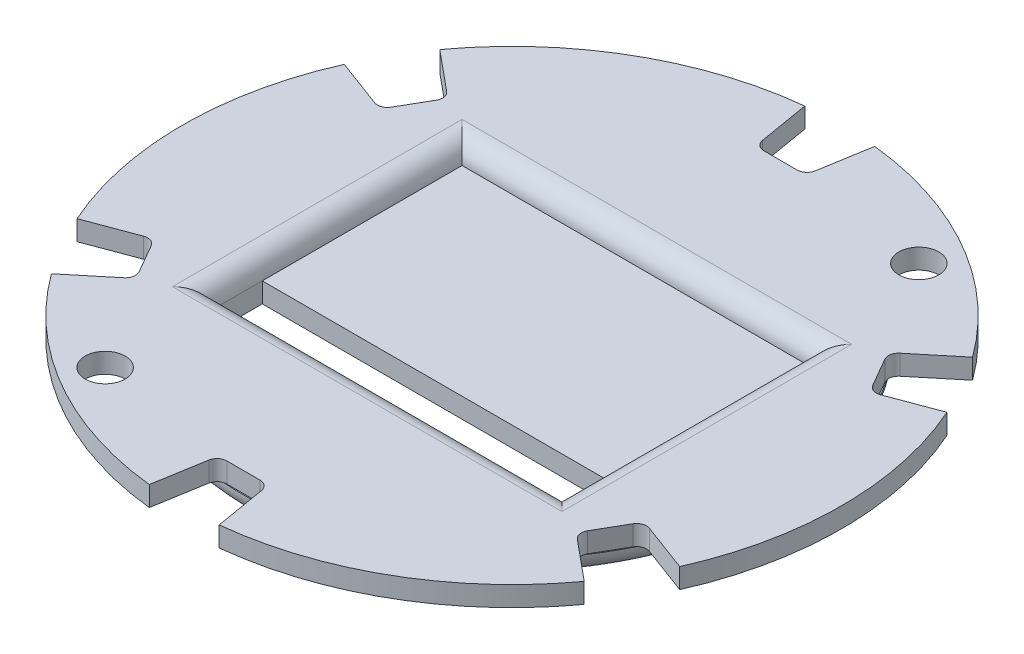
SolidWorks part; units mm, degrees
ref_plane "Front Plane" through (0, 0, 0) normal (0, 0, 1) x (1, 0, 0)
ref_plane "Top Plane" through (0, 0, 0) normal (0, 1, 0) x (1, 0, 0)
ref_plane "Right Plane" through (0, 0, 0) normal (1, 0, 0) x (0, 0, -1)
sketch "Sketch1" plane through (0, 0, 0) normal (0, 1, 0) x (1, 0, 0)
  circle A0 centre (0, 0) radius 33
  dimension "D1" = 66
extrude "Boss-Extrude1" add sketch "Sketch1" along normal blind 2
sketch "Sketch5" plane through (0, 0, 0) normal (0, -1, 0) x (1, 0, 0)
  circle A0 centre (0, 0) radius 27
  circle A2 centre (0, 0) radius 33 construction
  dimension "D1" = 6
extrude "Boss-Extrude2" add sketch "Sketch5" along normal blind 2
sketch "Sketch6" plane through (0, 0, 0) normal (0, -1, 0) x (1, 0, 0)
  line L1 (3.5, 32.8139) -> (2.6406, 27.7177)
  line L7 (-2.6406, 27.7177) -> (-3.5, 32.8139)
  line L9 (0, -33) -> (0, 33) construction
  line L10 (15.8503, -24.88) -> (-15.8503, 24.88) construction
  line L26 (32.8139, -3.5) -> (26.9836, -2.5168) [skipped]
  line L27 (30.1676, 13.3758) -> (25.3245, 11.572)
  line L28 (22.684, 16.1457) -> (26.6676, 19.438)
  line L29 (22.455, 14.8749) -> (24.1095, 12.0092)
  line L30 (26.9836, 2.5168) -> (32.8139, 3.5) [skipped]
  line L31 (-3.5, -32.8139) -> (-2.5168, -26.9836) [skipped]
  line L32 (26.6676, -19.438) -> (22.684, -16.1457)
  line L33 (25.3245, -11.572) -> (30.1676, -13.3758)
  line L34 (24.1095, -12.0092) -> (22.455, -14.8749)
  line L35 (2.5168, -26.9836) -> (3.5, -32.8139) [skipped]
  line L36 (-32.8139, 3.5) -> (-26.9836, 2.5168) [skipped]
  line L37 (-3.5, -32.8139) -> (-2.6406, -27.7177)
  line L38 (2.6406, -27.7177) -> (3.5, -32.8139)
  line L39 (1.6545, -26.884) -> (-1.6545, -26.884)
  line L40 (-26.9836, -2.5168) -> (-32.8139, -3.5) [skipped]
  line L66 (-1.6545, 26.884) -> (1.6545, 26.884)
  line L67 (-30.1676, -13.3758) -> (-25.3245, -11.572)
  line L68 (-22.684, -16.1457) -> (-26.6676, -19.438)
  line L69 (-22.455, -14.8749) -> (-24.1095, -12.0092)
  line L70 (-26.6676, 19.438) -> (-22.684, 16.1457)
  line L71 (-25.3245, 11.572) -> (-30.1676, 13.3758)
  line L72 (-24.1095, 12.0092) -> (-22.455, 14.8749)
  circle A0 centre (0, 0) radius 29.5
  circle A1 centre (0, 0) radius 33 construction
  circle A3 centre (0, 0) radius 29.5
  circle A5 centre (0, 0) radius 29.5
  circle A7 centre (0, 0) radius 29.5
  circle A9 centre (0, 0) radius 27 construction
  circle A10 centre (0, 0) radius 27 construction
  arc A11 (-3.5, 32.8139) -> (3.5, 32.8139) centre (0, 0) cw
  circle A12 centre (0, 0) radius 29.5
  circle A14 centre (0, 0) radius 29.5
  circle A16 centre (0, 0) radius 29.5
  arc A33 (32.8139, 3.5) -> (32.8139, -3.5) centre (0, 0) cw [skipped]
  arc A34 (3.5, -32.8139) -> (-3.5, -32.8139) centre (0, 0) cw [skipped]
  arc A35 (-32.8139, -3.5) -> (-32.8139, 3.5) centre (0, 0) cw [skipped]
  arc A53 (1.6545, 26.884) -> (2.6406, 27.7177) centre (1.6545, 27.884) ccw
  arc A54 (-2.6406, 27.7177) -> (-1.6545, 26.884) centre (-1.6545, 27.884) ccw
  arc A55 (26.6676, 19.438) -> (30.1676, 13.3758) centre (0, 0) cw
  arc A56 (24.1095, 12.0092) -> (25.3245, 11.572) centre (24.9755, 12.5092) ccw
  arc A57 (22.684, 16.1457) -> (22.455, 14.8749) centre (23.321, 15.3749) ccw
  arc A58 (30.1676, -13.3758) -> (26.6676, -19.438) centre (0, 0) cw
  arc A59 (22.455, -14.8749) -> (22.684, -16.1457) centre (23.321, -15.3749) ccw
  arc A60 (25.3245, -11.572) -> (24.1095, -12.0092) centre (24.9755, -12.5092) ccw
  arc A61 (3.5, -32.8139) -> (-3.5, -32.8139) centre (0, 0) cw
  arc A62 (-1.6545, -26.884) -> (-2.6406, -27.7177) centre (-1.6545, -27.884) ccw
  arc A63 (2.6406, -27.7177) -> (1.6545, -26.884) centre (1.6545, -27.884) ccw
  arc A64 (-26.6676, -19.438) -> (-30.1676, -13.3758) centre (0, 0) cw
  arc A65 (-24.1095, -12.0092) -> (-25.3245, -11.572) centre (-24.9755, -12.5092) ccw
  arc A66 (-22.684, -16.1457) -> (-22.455, -14.8749) centre (-23.321, -15.3749) ccw
  arc A67 (-30.1676, 13.3758) -> (-26.6676, 19.438) centre (0, 0) cw
  arc A68 (-22.455, 14.8749) -> (-22.684, 16.1457) centre (-23.321, 15.3749) ccw
  arc A69 (-25.3245, 11.572) -> (-24.1095, 12.0092) centre (-24.9755, 12.5092) ccw
  circle A75 centre (-15.8503, 24.88) radius 2
  circle A76 centre (0, 0) radius 29.5
  circle A77 centre (15.8503, -24.88) radius 2
  point P13 (0, 0)
  point P18 (0, 0)
  point P19 (2.5, 26.884)
  point P23 (0, 0)
  point P27 (0, 0)
  point P52 (0, 0)
  point P70 (0, 0)
  point P76 (0, 0)
  point P78 (-2.5, 26.884)
  point P87 (0, 0)
  point P90 (0, 0)
  dimension "D1" = 3.5
  dimension "D2" = 32.5
  dimension "D5" = 1
  dimension "D10" = 2
  dimension "D7" = 6
  dimension "D6" = 26.884
  dimension "D4" = 4
  dimension "D3" = 4
  dimension "D8" = 7
  dimension "D9" = 4
sketch "Sketch7" plane through (0, 2, 0) normal (0, 1, 0) x (1, 0, 0)
  line L1 (-17.5, 12.5) -> (17.5, 12.5)
  line L2 (-17.5, 12.5) -> (-17.5, -12.5)
  line L3 (-17.5, -12.5) -> (17.5, -12.5)
  line L4 (17.5, 12.5) -> (17.5, -12.5)
  line L5 (-17.5, 12.5) -> (17.5, -12.5) construction
  line L6 (-17.5, -12.5) -> (17.5, 12.5) construction
  point P0 (0, 0)
  dimension "D1" = 35
  dimension "D2" = 25
extrude "Cut-Extrude2" cut sketch "Sketch7" against normal blind 2
fillet "Fillet5" radius 2 1 edges at (0, -2, -27)
sketch "Sketch8" plane through (0, 2, 0) normal (0, 1, 0) x (1, 0, 0)
  line L0 (-17.5, -12.5) -> (17.5, -12.5) construction
  line L1 (-17.5, -7.5) -> (17.5, -7.5)
  line L2 (-17.5, -7.5) -> (-17.5, -12.5)
  line L3 (-17.5, -12.5) -> (17.5, -12.5)
  line L4 (17.5, -7.5) -> (17.5, -12.5)
  point P6 (0, -7.5)
  dimension "D1" = 35
  dimension "D2" = 5
  dimension "D3" = 5
extrude "Cut-Extrude3" cut sketch "Sketch8" against normal through all both and the other way through all
fillet "Fillet3" radius 2 4 edges at (0, 2, 12.5) (-17.5, 2, 0) (0, 2, -12.5) (17.5, 2, 0)
extrude "Cut-Extrude4" cut sketch "Sketch6" against normal blind 10 contours L1 A53 L66 A54 L7 A11 | L29 A56 L27 A55 L28 A57 | L33 A58 L32 A59 L34 A60 | L38 A61 L37 A62 L39 A63 | L67 A65 L69 A66 L68 A64 | L71 A67 L70 A68 L72 A69 | A77 | A75
